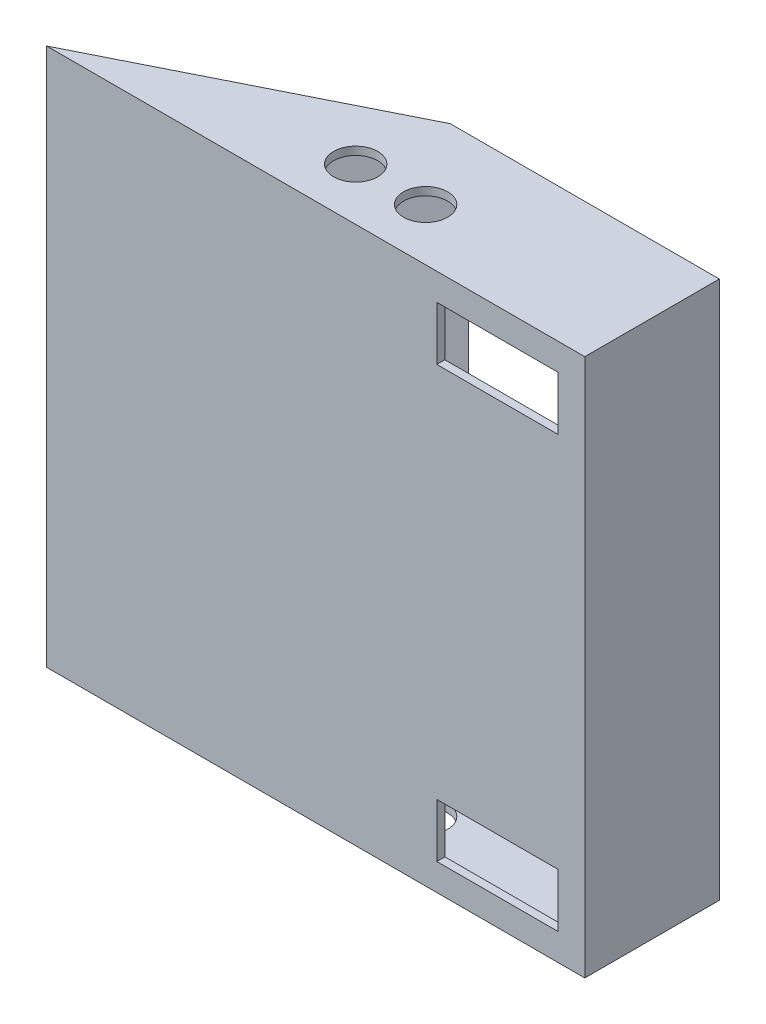
SolidWorks part; units mm, degrees
ref_plane "Alzado" through (0, 0, 0) normal (0, 0, 1) x (1, 0, 0)
ref_plane "Planta" through (0, 0, 0) normal (0, 1, 0) x (1, 0, 0)
ref_plane "Vista lateral" through (0, 0, 0) normal (1, 0, 0) x (0, 0, -1)
sketch "Croquis2" plane through (0, 0, 0) normal (0, 1, 0) x (1, 0, 0)
  line L4 (0, 0) -> (200, 0)
  line L5 (200, 0) -> (200, 50)
  line L6 (200, 50) -> (100, 50)
  line L9 (100, 50) -> (0, 0)
  dimension "D1" = 50
  dimension "D2" = 200
  dimension "D3" = 100
extrude "Saliente-Extruir1" add sketch "Croquis2" along normal blind 200
shell "Vaciado2" thickness 3 removed face at (150, 100, -50)
sketch "Croquis4" plane through (0, 0, 0) normal (0, -1, 0) x (1, 0, 0)
  line L0 (0, 0) -> (200, 0) construction
  circle A0 centre (121.4428, -19.4) radius 8.2
  circle A1 centre (95.4428, -19.4) radius 8.2
  dimension "D1" = 16.4
  dimension "D2" = 26
  dimension "D3" = 19.4
extrude "Cortar-Extruir2" cut sketch "Croquis4" against normal through all
sketch "Croquis7" plane through (0, 0, -3) normal (0, 0, -1) x (-1, 0, 0)
  line L0 (-197, 197) -> (-197, 3) construction
  line L1 (-190, 30) -> (-145, 30)
  line L2 (-190, 30) -> (-190, 10)
  line L3 (-190, 10) -> (-145, 10)
  line L4 (-145, 30) -> (-145, 10)
  line L5 (-197, 3) -> (-106.7082, 3) construction
  line L6 (-200, 100) -> (0, 100) construction
  line L7 (-200, 200) -> (-200, 0) construction
  line L8 (0, 200) -> (0, 0) construction
  line L9 (-145, 170) -> (-145, 190)
  line L10 (-190, 190) -> (-145, 190)
  line L11 (-190, 170) -> (-190, 190)
  line L12 (-190, 170) -> (-145, 170)
  dimension "D1" = 20
  dimension "D2" = 45
  dimension "D3" = 7
  dimension "D4" = 7
extrude "Cortar-Extruir4" cut sketch "Croquis7" against normal through all
shell "Vaciado1" thickness 3 rebuild error yes
